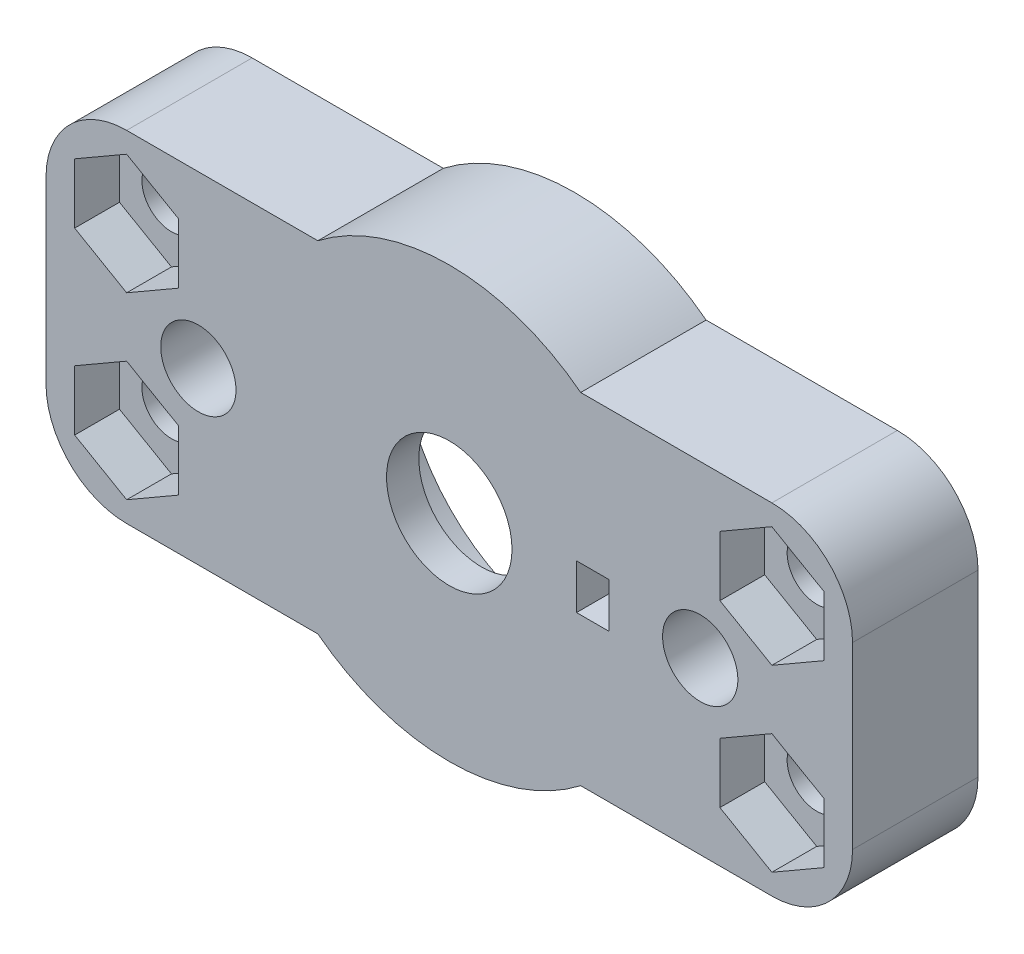
SolidWorks part; units mm, degrees
ref_plane "Front Plane" through (0, 0, 0) normal (0, 0, 1) x (1, 0, 0)
ref_plane "Top Plane" through (0, 0, 0) normal (0, 1, 0) x (1, 0, 0)
ref_plane "Right Plane" through (0, 0, 0) normal (1, 0, 0) x (0, 0, -1)
sketch "Sketch1" plane through (0, 0, 0) normal (0, 0, 1) x (1, 0, 0)
  circle A0 centre (0, 0) radius 9.5 construction
  circle A1 centre (0, 0) radius 2.5 construction
  dimension "D1" = 19
  dimension "D2" = 5
sketch "Sketch2" plane through (0, 0, 0) normal (0, 0, 1) x (1, 0, 0)
  line L0 (-18, 9.5) -> (-7.3314, 9.5)
  line L5 (0, 0) -> (0, 12) construction
  line L6 (0, 0) -> (-30.5723, 0) construction
  line L7 (-22.5, 5) -> (-22.5, -5)
  line L8 (22.5, 5) -> (22.5, -5)
  line L9 (18, 9.5) -> (7.3314, 9.5)
  line L10 (18, -9.5) -> (7.3314, -9.5)
  line L11 (-18, -9.5) -> (-7.3314, -9.5)
  arc A1 (-7.3314, 9.5) -> (7.3314, 9.5) centre (0, 0) cw
  circle A3 centre (0, 0) radius 9.5 construction
  arc A4 (-7.3314, -9.5) -> (7.3314, -9.5) centre (0, 0) ccw
  arc A5 (22.5, 5) -> (18, 9.5) centre (18, 5) ccw
  arc A6 (18, -9.5) -> (22.5, -5) centre (18, -5) ccw
  arc A7 (-22.5, -5) -> (-18, -9.5) centre (-18, -5) ccw
  arc A8 (-22.5, 5) -> (-18, 9.5) centre (-18, 5) cw
  circle A10 centre (-18, 5) radius 1.65
  circle A11 centre (18, 5) radius 1.65
  circle A12 centre (18, -5) radius 1.65
  circle A13 centre (-18, -5) radius 1.65
  point P0 (0, 0)
  point P8 (22.5, 9.5)
  point P21 (22.5, 0)
  point P22 (-22.5, 0)
  point P23 (22.5, -9.5)
  point P26 (-22.5, -9.5)
  point P29 (-22.5, 9.5)
  dimension "D1" = 2.5
  dimension "D2" = 4.5
  dimension "D3" = 3.3
  dimension "D4" = 10
  dimension "D5" = 45
extrude "Boss-Extrude1" add sketch "Sketch2" along normal blind 7
sketch "Sketch3" plane through (0, 0, 0) normal (0, 0, 1) x (1, 0, 0)
  circle A3 centre (0, 0) radius 9.7
  circle A4 centre (0, 0) radius 9.7
  dimension "D1" = 0.2
extrude "Cut-Extrude1" cut sketch "Sketch3" along normal blind 5
sketch "Sketch4" plane through (0, 0, 5) normal (0, 0, -1) x (-1, 0, 0)
  circle A0 centre (0, 0) radius 7.5
  dimension "D1" = 15
extrude "Cut-Extrude2" cut sketch "Sketch4" against normal blind 5
sketch "Sketch5" plane through (0, 0, 7) normal (0, 0, 1) x (1, 0, 0)
  line L0 (0, 0) -> (0, 12) construction
  line L1 (-18, 8.3486) -> (-20.9, 6.6743)
  line L2 (-20.9, 6.6743) -> (-20.9, 3.3257)
  line L3 (-20.9, 3.3257) -> (-18, 1.6514)
  line L4 (-18, 1.6514) -> (-15.1, 3.3257)
  line L5 (-15.1, 3.3257) -> (-15.1, 6.6743)
  line L6 (-15.1, 6.6743) -> (-18, 8.3486)
  line L7 (15.1, 6.6743) -> (18, 8.3486)
  line L8 (-22.5, 5) -> (-22.5, -5) construction
  line L9 (-22.5, 0) -> (0, 0) construction
  line L10 (15.1, 3.3257) -> (15.1, 6.6743)
  line L11 (18, 1.6514) -> (15.1, 3.3257)
  line L12 (20.9, 3.3257) -> (18, 1.6514)
  line L13 (20.9, 6.6743) -> (20.9, 3.3257)
  line L14 (18, 8.3486) -> (20.9, 6.6743)
  line L15 (15.1, -3.3257) -> (15.1, -6.6743)
  line L16 (18, -1.6514) -> (15.1, -3.3257)
  line L17 (20.9, -3.3257) -> (18, -1.6514)
  line L18 (20.9, -6.6743) -> (20.9, -3.3257)
  line L19 (18, -8.3486) -> (20.9, -6.6743)
  line L20 (15.1, -6.6743) -> (18, -8.3486)
  line L21 (-15.1, -6.6743) -> (-18, -8.3486)
  line L22 (-15.1, -3.3257) -> (-15.1, -6.6743)
  line L23 (-18, -1.6514) -> (-15.1, -3.3257)
  line L24 (-20.9, -3.3257) -> (-18, -1.6514)
  line L25 (-20.9, -6.6743) -> (-20.9, -3.3257)
  line L26 (-18, -8.3486) -> (-20.9, -6.6743)
  circle A0 centre (-18, 5) radius 2.9 construction
  arc A1 (7.3314, 9.5) -> (-7.3314, 9.5) centre (0, 0) ccw construction
  dimension "D1" = 5.8
extrude "Cut-Extrude3" cut sketch "Sketch5" against normal blind 2.5
sketch "Sketch6" plane through (0, 0, 7) normal (0, 0, 1) x (1, 0, 0)
  circle A0 centre (0, 0) radius 7.5
  circle A1 centre (0, 0) radius 7.5 construction
  circle A2 centre (0, 0) radius 3.5
  dimension "D1" = 7
extrude "Boss-Extrude2" add sketch "Sketch6" against normal blind 1.8
sketch "Sketch7" plane through (0, 0, 7) normal (0, 0, 1) x (1, 0, 0)
  line L0 (0, 0) -> (8, 0) construction
  line L2 (7.1, -1.25) -> (8.9, -1.25)
  line L3 (7.1, -1.25) -> (7.1, 1.25)
  line L4 (7.1, 1.25) -> (8.9, 1.25)
  line L5 (8.9, -1.25) -> (8.9, 1.25)
  line L6 (7.1, -1.25) -> (8.9, 1.25) construction
  line L7 (7.1, 1.25) -> (8.9, -1.25) construction
  point P7 (7.7896, 0)
  point P8 (8.1121, 0)
  dimension "D1" = 1.8
  dimension "D2" = 2.5
  dimension "D3" = 8
extrude "Cut-Extrude4" cut sketch "Sketch7" against normal blind 2.5
sketch "Sketch8" plane through (0, 0, 7) normal (0, 0, 1) x (1, 0, 0)
  line L0 (0, 0) -> (0, 12) construction
  circle A0 centre (-14, 0) radius 2.1
  arc A1 (7.3314, 9.5) -> (-7.3314, 9.5) centre (0, 0) ccw construction
  circle A2 centre (14, 0) radius 2.1
  dimension "D2" = 4.2
  dimension "D1" = 14
extrude "Cut-Extrude5" cut sketch "Sketch8" against normal blind 3
